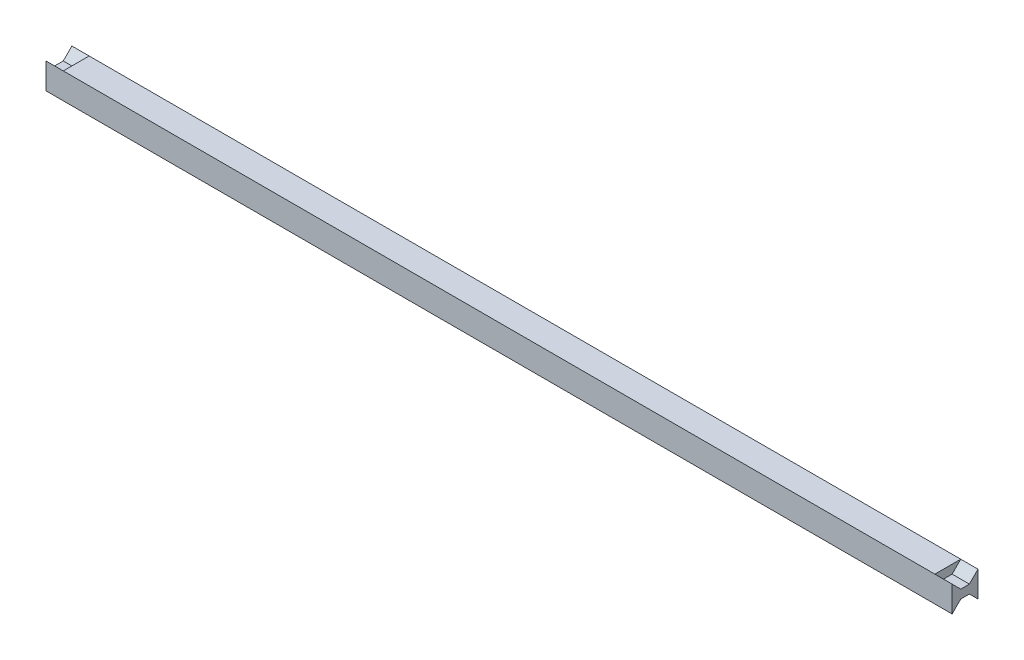
SolidWorks part; units mm, degrees
ref_plane "Přední rovina" through (0, 0, 0) normal (0, 0, 1) x (1, 0, 0)
ref_plane "Horní rovina" through (0, 0, 0) normal (0, 1, 0) x (1, 0, 0)
ref_plane "Pravá rovina" through (0, 0, 0) normal (1, 0, 0) x (0, 0, -1)
sketch "Skica1" plane through (0, 0, 0) normal (0, 1, 0) x (1, 0, 0)
  line L0 (0, 0) -> (202, 0)
  line L1 (202, 0) -> (202, 6)
  line L2 (202, 6) -> (0, 6)
  line L3 (0, 6) -> (0, 0)
  dimension "D1" = 6
  dimension "D2" = 202
extrude "Přidat vysunutím1" add sketch "Skica1" along normal blind 6
sketch "Skica2" plane through (0, 0, 0) normal (-1, 0, 0) x (0, 0, 1)
  line L6 (-6, 6) -> (-6, 0)
  line L7 (-6, 0) -> (-4, 2)
  line L8 (-4, 2) -> (-2, 2)
  line L9 (-2, 2) -> (0, 0)
  line L10 (0, 0) -> (0, 6)
  line L11 (0, 6) -> (-2, 4)
  line L12 (-2, 4) -> (-4, 4)
  line L13 (-4, 4) -> (-6, 6)
  line L14 (0, 0) -> (-6, 0) construction
  line L15 (0, 6) -> (-6, 6) construction
  dimension "D1" = 2
  dimension "D2" = 2
  dimension "D3" = 2
  dimension "D4" = 2
  dimension "D5" = 45
  dimension "D6" = 45
extrude "Přidat vysunutím2" add sketch "Skica2" along normal blind 4
sketch "Skica3" plane through (202, 0, 0) normal (1, 0, 0) x (0, 0, -1)
  line L5 (0, 6) -> (0, 0)
  line L7 (0, 0) -> (2, 2)
  line L8 (2, 2) -> (4, 2)
  line L9 (4, 2) -> (6, 0)
  line L10 (6, 0) -> (6, 6)
  line L11 (6, 6) -> (4, 4)
  line L12 (4, 4) -> (2, 4)
  line L13 (2, 4) -> (0, 6)
  line L14 (0, 0) -> (6, 0) construction
  line L15 (0, 6) -> (6, 6) construction
  dimension "D1" = 2
  dimension "D2" = 2
  dimension "D3" = 2
  dimension "D4" = 2
  dimension "D5" = 45
  dimension "D6" = 45
extrude "Přidat vysunutím3" add sketch "Skica3" along normal blind 4
